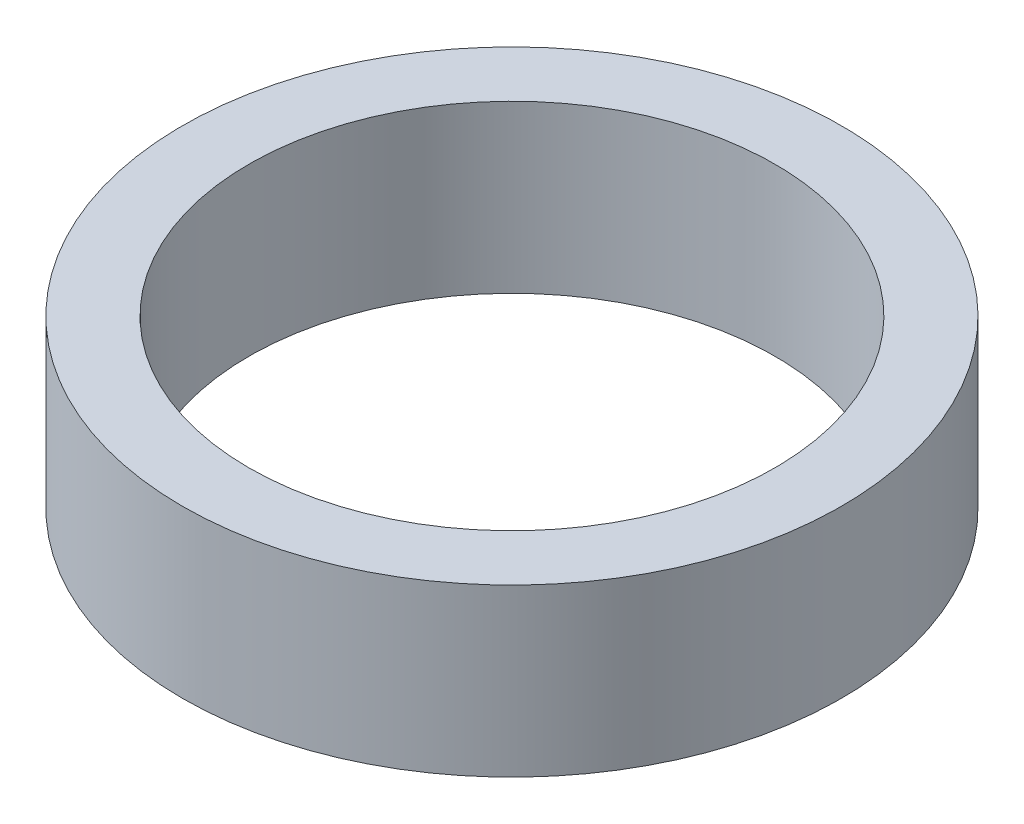
SolidWorks part; units mm, degrees
ref_plane "Front Plane" through (0, 0, 0) normal (0, 0, 1) x (1, 0, 0)
ref_plane "Top Plane" through (0, 0, 0) normal (0, 1, 0) x (1, 0, 0)
ref_plane "Right Plane" through (0, 0, 0) normal (1, 0, 0) x (0, 0, -1)
sketch "Sketch1" plane through (0, 0, 0) normal (0, 1, 0) x (1, 0, 0)
  circle A0 centre (0, 0) radius 15.725
  circle A1 centre (0, 0) radius 12.55
  dimension "D1" = 25.1
  dimension "D2" = 3.175
extrude "Boss-Extrude1" add sketch "Sketch1" along normal mid plane 7.9375
